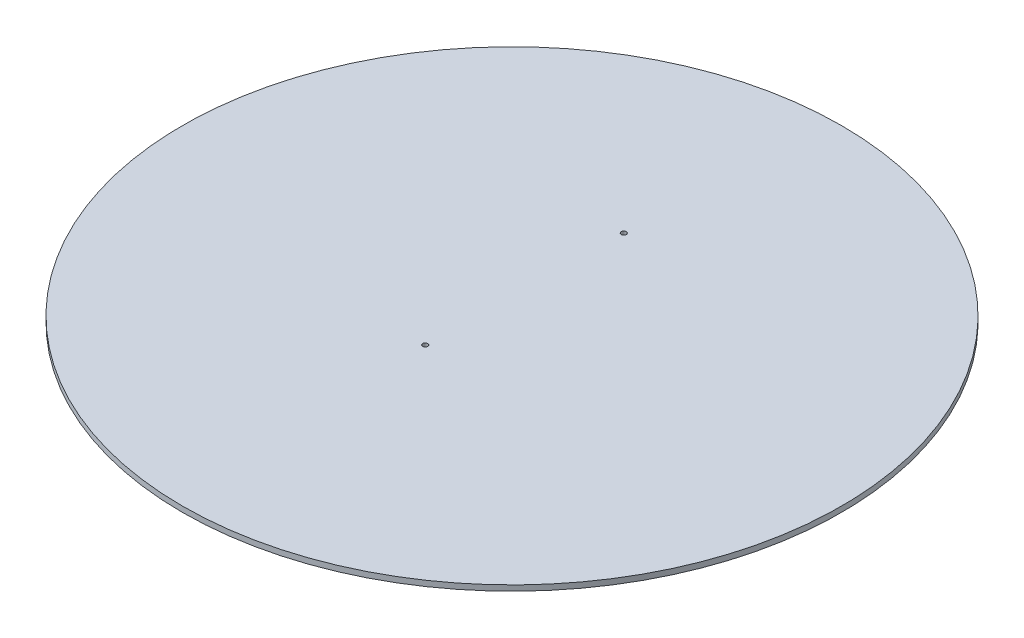
SolidWorks part; units mm, degrees
material "AISI 1020"
ref_plane "Front Plane" through (0, 0, 0) normal (0, 0, 1) x (1, 0, 0)
ref_plane "Top Plane" through (0, 0, 0) normal (0, 1, 0) x (1, 0, 0)
ref_plane "Right Plane" through (0, 0, 0) normal (1, 0, 0) x (0, 0, -1)
sketch "Sketch2" plane through (0, 0, 0) normal (0, 1, 0) x (1, 0, 0)
  circle A0 centre (0, 0) radius 304.8
  dimension "D1" = 609.6
extrude "Boss-Extrude1" add sketch "Sketch2" along normal blind 5.08
extrude "Cut-Extrude1" cut sketch "Sketch3" against normal through all
sketch "Sketch3" plane through (-67.0651, 76.0569, -93.3014) normal (0.1079, 0.9936, 0.0319) x (0.9942, -0.108, -0.0006)
  circle A0 centre (57.5716, -158.8222) radius 2.3495
  circle A1 centre (59.8998, 22.5177) radius 2.3495
